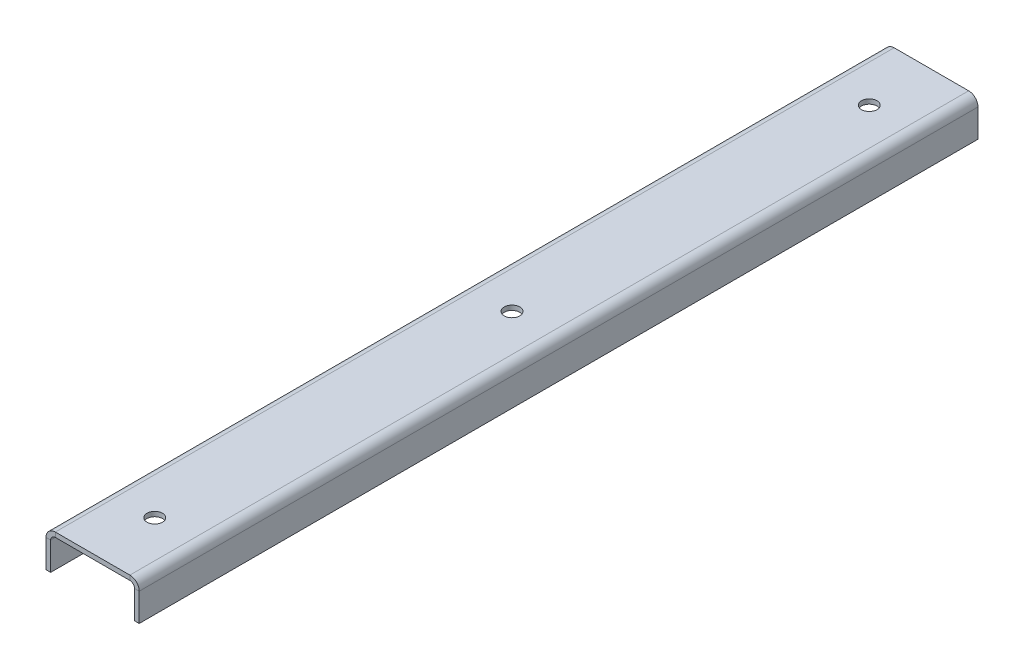
SolidWorks part; units mm, degrees
note: The reader was unsure of these and kept them because the rebuilt part matched: bend radius of "Базовая кромка1", "Основание1", "Основание2".
material "Оцинкованная сталь"
ref_plane "Спереди" through (0, 0, 0) normal (0, 0, 1) x (1, 0, 0)
ref_plane "Сверху" through (0, 0, 0) normal (0, 1, 0) x (1, 0, 0)
ref_plane "Справа" through (0, 0, 0) normal (1, 0, 0) x (0, 0, -1)
sketch "Эскиз1" plane through (0, 0, 0) normal (0, 0, 1) x (1, 0, 0)
  line L0 (-13.5, 0) -> (13.5, 0)
  line L1 (13.5, 0) -> (13.5, -10.5)
  line L2 (-13.5, 0) -> (-13.5, -10.5)
  point P3 (0, 0)
  dimension "D1" = 10.5
  dimension "D2" = 27
base flange "Базовая кромка1" sketch "Эскиз1" end condition mid plane depth 270 reverse direction no thickness 1.5 reverse thickness direction no bend radius 1.5
bend "Основание1" bend radius 1.5 bend angle 90 parameters "D5"=1
bend "Основание2" bend radius 1.5 bend angle 90 parameters "D5"=2
sketch "Эскиз2" plane through (0, 1.5, 0) normal (0, 1, 0) x (1, 0, 0)
  line L0 (-15, -135) -> (-15, 135) construction
  circle A0 centre (0, 0) radius 2.5
  circle A1 centre (0, 115) radius 2.5
  circle A2 centre (0, 230) radius 2.5
  circle A3 centre (0, 345) radius 2.5
  circle A4 centre (0, 460) radius 2.5
  circle A5 centre (0, -115) radius 2.5
  circle A6 centre (0, 0) radius 2.5
  circle A7 centre (0, 115) radius 2.5
  circle A8 centre (0, 230) radius 2.5
  circle A9 centre (0, 345) radius 2.5
  circle A10 centre (0, -230) radius 2.5
  circle A11 centre (0, -115) radius 2.5
  circle A12 centre (0, 0) radius 2.5
  circle A13 centre (0, 115) radius 2.5
  circle A14 centre (0, 230) radius 2.5
  circle A15 centre (0, -345) radius 2.5
  circle A16 centre (0, -230) radius 2.5
  circle A17 centre (0, -115) radius 2.5
  circle A18 centre (0, 0) radius 2.5
  circle A19 centre (0, 115) radius 2.5
  circle A20 centre (0, -460) radius 2.5
  circle A21 centre (0, -345) radius 2.5
  circle A22 centre (0, -230) radius 2.5
  circle A23 centre (0, -115) radius 2.5
  circle A24 centre (0, 0) radius 2.5
  dimension "D1" = 5
  dimension "D2" = 15
  dimension "D5" = 115
  dimension "D6" = 115
  dimension "D3" = 5
  dimension "D4" = 5
extrude "Вырез-Вытянуть1" cut sketch "Эскиз2" against normal blind 10 contours A0 | A4 | A5 | A10 | A15 | A20 | A1 | A2 | A3
sketch "Сгиб-Линии1" [suppressed] plane through (0, 0, 0) normal (0, 1, 0) x (1, 0, 0)
sketch "Граничная рамка1" [suppressed] plane through (0, 0, 0) normal (0, 1, 0) x (1, 0, 0)
sheet metal parameters "Листовой металл3" thickness 1.5 parameters "D1"=1.5
flat pattern "Развертка3" [suppressed]
sketch "Сгиб-Линии2" plane through (0, 0, 0) normal (0, -1, 0) x (-1, 0, 0)
  line L0 (-13.7671, -135) -> (-13.7671, 135) construction
  line L1 (13.7671, 135) -> (13.7671, -135) construction
  line L2 (-13.7671, -135) -> (-13.7671, 135) construction
  line L3 (13.7671, 135) -> (13.7671, -135) construction
sketch3d "Граничная рамка2" [suppressed]
  line L0 (-38.0343, 0, 0) -> (-38.0343, 270, 0) construction
  line L1 (11.0343, 0, 0) -> (11.0343, 270, 0) construction
  line L2 (-38.0343, 0, 0) -> (11.0343, 0, 0) construction
  line L3 (-38.0343, 270, 0) -> (11.0343, 270, 0) construction
bend of the flat pattern "Плоское состояние-<Основание1>1"
bend of the flat pattern "Плоское состояние-<Основание2>1"
sheet metal parameters "Листовой металл4" thickness 1.5 parameters "D1"=1.5
flat pattern "Развертка3"
sketch "Сгиб-Линии2" plane through (0, 0, 0) normal (0, -1, 0) x (-1, 0, 0)
  line L0 (-13.7671, -135) -> (-13.7671, 135) construction
  line L1 (13.7671, 135) -> (13.7671, -135) construction
  line L2 (-13.7671, -135) -> (-13.7671, 135) construction
  line L3 (13.7671, 135) -> (13.7671, -135) construction
sketch3d "Граничная рамка2" [suppressed]
  line L0 (-38.0343, 0, 0) -> (-38.0343, 270, 0) construction
  line L1 (11.0343, 0, 0) -> (11.0343, 270, 0) construction
  line L2 (-38.0343, 0, 0) -> (11.0343, 0, 0) construction
  line L3 (-38.0343, 270, 0) -> (11.0343, 270, 0) construction
bend of the flat pattern "Плоское состояние-<Основание1>1"
bend of the flat pattern "Плоское состояние-<Основание2>1"
